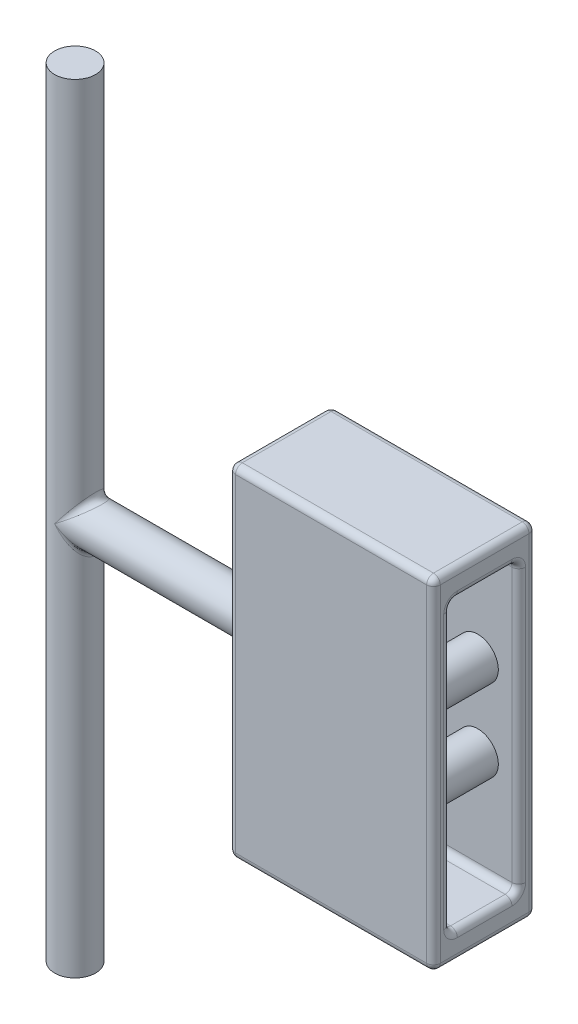
SolidWorks part; units mm, degrees
material "AISI 304"
ref_plane "Front Plane" through (0, 0, 0) normal (0, 0, 1) x (1, 0, 0)
ref_plane "Top Plane" through (0, 0, 0) normal (0, 1, 0) x (1, 0, 0)
ref_plane "Right Plane" through (0, 0, 0) normal (1, 0, 0) x (0, 0, -1)
sketch "Sketch1" plane through (0, 0, 0) normal (0, 1, 0) x (1, 0, 0)
  circle A0 centre (0, 0) radius 3
  dimension "D1" = 6
extrude "Boss-Extrude1" add sketch "Sketch1" along normal blind 114
sketch "Sketch3" plane through (0, 0, 0) normal (1, 0, 0) x (0, 0, -1)
  circle A0 centre (0, 57) radius 3
  dimension "D2" = 6
  dimension "D1" = 57
extrude "Boss-Extrude2" add sketch "Sketch3" along normal blind 30
sketch "Sketch4" plane through (30, 0, 0) normal (1, 0, 0) x (0, 0, -1)
  line L1 (-7.5, 32) -> (7.5, 32)
  line L2 (-7.5, 32) -> (-7.5, 82)
  line L3 (-7.5, 82) -> (7.5, 82)
  line L4 (7.5, 32) -> (7.5, 82)
  line L5 (-7.5, 32) -> (7.5, 82) construction
  line L6 (-7.5, 82) -> (7.5, 32) construction
  point P0 (0, 57)
  dimension "D1" = 50
  dimension "D2" = 15
extrude "Boss-Extrude3" add sketch "Sketch4" along normal blind 30
sketch "Sketch6" plane through (60, 0, 0) normal (1, 0, 0) x (0, 0, -1)
  line L1 (-5, 36) -> (5, 36)
  line L2 (-5, 36) -> (-5, 78)
  line L3 (-5, 78) -> (5, 78)
  line L4 (5, 36) -> (5, 78)
  line L5 (-5, 36) -> (5, 78) construction
  line L6 (-5, 78) -> (5, 36) construction
  circle A0 centre (0, 57) radius 3 construction
  point P0 (0, 57)
  dimension "D1" = 10
  dimension "D2" = 42
extrude "Cut-Extrude1" cut sketch "Sketch6" against normal blind 20
sketch "Sketch7" plane through (0, 0, -5) normal (0, 0, 1) x (1, 0, 0)
  line L0 (54, 82) -> (54, 32) construction
  line L1 (60, 82) -> (30, 82) construction
  line L2 (60, 32) -> (30, 32) construction
  line L5 (30, 57) -> (60, 57) construction
  line L8 (30, 82) -> (30, 32) construction
  line L9 (60, 82) -> (60, 32) construction
  circle A1 centre (54, 63) radius 3
  circle A2 centre (54, 51) radius 3
  dimension "D1" = 6
  dimension "D2" = 6
  dimension "D4" = 6
  dimension "D3" = 6
  dimension "D5" = 6
  dimension "D6" = 0
  dimension "D7" = 0
fillet "Fillet2" radius 1 3 edges at (3, 60, 0) (3, 54, 0) (30, 57, -3)
extrude "Boss-Extrude4" add sketch "Sketch7" along normal blind 10
fillet "Fillet3" radius 1 24 edges at (50, 36, -5) (50, 36, 5) (50, 78, -5) (50, 78, 5) (40, 36, 0) (40, 57, 5) (40, 78, 0) (40, 57, -5) (30, 32, 0) (45, 32, -7.5) (30, 57, -7.5) (60, 32, 0) (60, 57, -7.5) (60, 57, 5) (60, 36, 0) (60, 57, -5) (60, 78, 0) (45, 82, -7.5) (60, 82, 0) (30, 82, 0) (45, 82, 7.5) (60, 57, 7.5) (45, 32, 7.5) (30, 57, 7.5)
